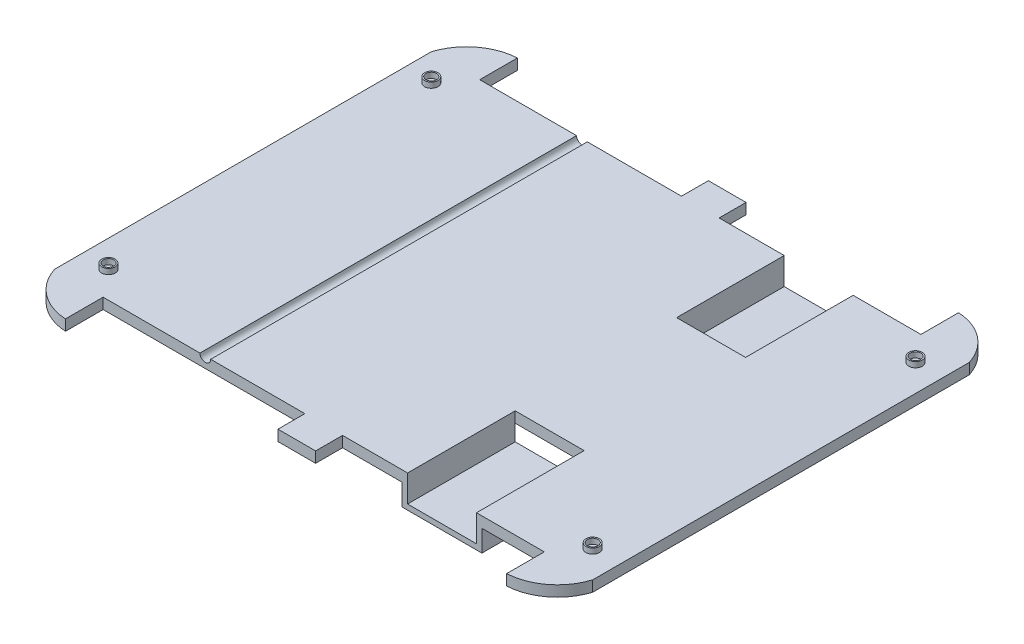
SolidWorks part; units mm, degrees
ref_plane "Front Plane" through (0, 0, 0) normal (0, 0, 1) x (1, 0, 0)
ref_plane "Top Plane" through (0, 0, 0) normal (0, 1, 0) x (1, 0, 0)
ref_plane "Right Plane" through (0, 0, 0) normal (1, 0, 0) x (0, 0, -1)
sketch "Sketch1" plane through (0, 0, 0) normal (0, 1, 0) x (1, 0, 0)
  line L0 (-75.9051, 0) -> (0, 0) construction
  line L1 (-3.5, 35) -> (-3.5, 40)
  line L2 (-50, -35) -> (-50, 35)
  line L3 (-41, 42) -> (0, 42)
  line L4 (3.5, 35) -> (3.5, 40)
  line L5 (41, 35) -> (3.5, 35)
  line L7 (-75.9051, 35) -> (0, 35) construction
  line L8 (-41, 35) -> (-41, 42)
  line L9 (0, -65.306) -> (0, 75.0053) construction
  line L10 (41, 35) -> (41, 42)
  line L12 (-41, 35) -> (-3.5, 35)
  line L13 (-3.5, 40) -> (3.5, 40)
  line L14 (50, 35) -> (41, 42)
  line L15 (50, -35) -> (50, 35)
  line L16 (50, -35) -> (41, -42)
  line L17 (41, -35) -> (41, -42)
  line L18 (41, -35) -> (3.5, -35)
  line L19 (3.5, -35) -> (3.5, -40)
  line L20 (-3.5, -40) -> (3.5, -40)
  line L21 (-3.5, -35) -> (-3.5, -40)
  line L22 (-41, -35) -> (-3.5, -35)
  line L23 (-41, -35) -> (-41, -42)
  line L24 (-50, -35) -> (-41, -42)
  arc A0 (-50, 35) -> (-41, 42) centre (-40.456, 32.0148) cw
  arc A1 (-50, -35) -> (-41, -42) centre (-40.456, -32.0148) ccw
  arc A2 (50, -35) -> (41, -42) centre (40.456, -32.0148) cw
  arc A3 (50, 35) -> (41, 42) centre (40.456, 32.0148) ccw
  point P1 (0, 0)
  point P10 (0, 40)
  point P26 (50, 0)
  point P35 (-50, 0)
  dimension "D7" = 10
  dimension "D1" = 42
  dimension "D2" = 50
  dimension "D3" = 35
  dimension "D4" = 9
  dimension "D5" = 3.5
  dimension "D6" = 40
extrude "Boss-Extrude2" add sketch "Sketch1" along normal blind 2 contours L2 L24 L23 L22 L21 L20 L19 L18 L17 L16 L15 L14 L10 L5 L4 L13 L1 L12 L8 | L24 A1 | A2 L16 | L14 A3 region at (-0.0881, 0, -0.0749) region at (-45.9417, 0, 39.0679) region at (45.9417, 0, -39.0679) region at (45.9417, 0, 39.0679)
sketch "Sketch4" plane through (0, 0, 0) normal (0, 0, 1) x (1, 0, 0)
  line L3 (-41, 0) -> (-3.5, 0) construction
  circle A0 centre (-22, 2) radius 1
  dimension "D1" = 2
  dimension "D6" = 2
  dimension "D4" = 22
extrude "Cut-Extrude4" cut sketch "Sketch4" against normal through all both and the other way through all
ref_plane "Plane1" through (0, 0, 50) normal (0, 0, 1) x (1, 0, 0)
sketch "Sketch6" plane through (0, 0, 50) normal (0, 0, 1) x (1, 0, 0)
  line L0 (41, 0) -> (3.5, 0) construction
  line L1 (21, 2) -> (21, 1)
  line L2 (21, 1) -> (23, 1)
  line L3 (23, 1) -> (23, 2)
  line L4 (15.595, 0) -> (14.595, 0)
  line L5 (15.595, -3) -> (28.405, -3)
  line L6 (15.595, -3) -> (15.595, 8)
  line L7 (15.595, 8) -> (28.405, 8)
  line L8 (28.405, -3) -> (28.405, 8)
  line L9 (14.595, 0) -> (14.595, -4)
  line L10 (14.595, -4) -> (29.405, -4)
  line L11 (29.405, -4) -> (29.405, 0)
  line L12 (29.405, 0) -> (28.405, 0)
  line L13 (15.595, 0) -> (15.595, 2)
  line L14 (15.595, 2) -> (28.405, 2)
  line L15 (41, 2) -> (3.5, 2) construction
  line L16 (28.405, 2) -> (28.405, 0)
  arc A0 (23, 2) -> (21, 2) centre (22, 2) ccw
  dimension "D2" = 2
  dimension "D1" = 22
  dimension "D3" = 2
  dimension "D4" = 4
  dimension "D5" = 6.405
  dimension "D6" = 6.405
  dimension "D7" = 6
  dimension "D8" = 1
  dimension "D9" = 1
  dimension "D10" = 1
extrude "Boss-Extrude3" add sketch "Sketch6" against normal blind 20 from offset 15 contours L11 L12 L8 L5 L6 L4 L9 L10 region at (15.4416, -1.5, 50) offset against normal yes
extrude "Boss-Extrude4" add sketch "Sketch6<3>" along normal blind 20 from offset 85 contours L11 L12 L8 L5 L6 L4 L9 L10 region at (15.4416, -1.5, 50) offset against normal yes
sketch "Sketch6<3>" plane through (0, 0, 50) normal (0, 0, 1) x (1, 0, 0) same geometry as "Sketch6"
extrude "Cut-Extrude5" cut sketch "Sketch6<4>" against normal blind 40 and the other way blind 1 from offset 5 contours L14 L6 L5 L8 L3 L2 L1 | L14 L1 L2 L3 region at (22, 1.5, 50) region at (22, -0.5645, 50)
sketch "Sketch6<4>" plane through (0, 0, 50) normal (0, 0, 1) x (1, 0, 0) same geometry as "Sketch6"
extrude "Cut-Extrude6" cut sketch "Sketch6<6>" against normal blind 20 from offset 65 contours L14 L6 L5 L8 L3 L2 L1 | L14 L1 L2 L3 region at (22, 1.5, 50) region at (22, -0.5645, 50) offset against normal yes
sketch "Sketch6<6>" plane through (0, 0, 50) normal (0, 0, 1) x (1, 0, 0) same geometry as "Sketch6"
ref_plane "Plane3" through (0, 0, 50) normal (0, 0, 1) x (1, 0, 0)
sketch "Sketch11" plane through (0, 2, 0) normal (0, 1, 0) x (1, 0, 0)
  line L0 (0, 0) -> (0, 43.4015) construction
  line L1 (0, 0) -> (-54.0483, 0) construction
  line L3 (-50, -35) -> (-50, 35) construction
  line L4 (-41, 35) -> (-23, 35) construction
  circle A0 centre (-45, 30) radius 1
  circle A1 centre (-45, 30) radius 1.25
  circle A2 centre (45, 30) radius 1
  circle A3 centre (45, 30) radius 1.25
  circle A4 centre (-45, -30) radius 1
  circle A5 centre (-45, -30) radius 1.25
  circle A6 centre (45, -30) radius 1.25
  circle A7 centre (45, -30) radius 1
  dimension "D1" = 2
  dimension "D2" = 5
  dimension "D4" = 2.5
  dimension "D3" = 5
extrude "Boss-Extrude6" add sketch "Sketch11" along normal blind 1
sketch "Sketch12" plane through (0, 2, 0) normal (0, 1, 0) x (1, 0, 0)
  line L22 (28.405, 35) -> (28.405, 15)
  line L23 (28.405, 35) -> (28.405, 15)
  line L24 (28.405, 15) -> (15.595, 15)
  line L25 (50, -35) -> (50, 35)
  line L26 (28.405, 15) -> (15.595, 15)
  line L27 (41, 42) -> (41, 35)
  line L28 (41, 35) -> (28.405, 35)
  line L29 (15.595, 15) -> (15.595, 35)
  line L30 (15.595, 15) -> (15.595, 35)
  line L31 (15.595, 35) -> (3.5, 35)
  line L32 (15.595, 35) -> (3.5, 35)
  line L33 (3.5, 35) -> (3.5, 40)
  line L34 (3.5, 40) -> (-3.5, 40)
  line L35 (-3.5, 40) -> (-3.5, 35)
  line L36 (-3.5, 35) -> (-21, 35)
  line L37 (-21, 35) -> (-21, -35)
  line L38 (-21, -35) -> (-3.5, -35)
  line L39 (-3.5, -35) -> (-3.5, -40)
  line L40 (-3.5, -40) -> (3.5, -40)
  line L41 (3.5, -40) -> (3.5, -35)
  line L42 (3.5, -35) -> (15.595, -35)
  line L43 (15.595, -35) -> (15.595, -15)
  line L44 (15.595, -15) -> (28.405, -15)
  line L45 (28.405, -15) -> (28.405, -35)
  line L46 (28.405, -35) -> (41, -35)
  line L47 (41, -35) -> (41, -42)
  line L49 (50, -35) -> (50, 35)
  line L51 (41, 42) -> (41, 35)
  line L52 (41, 35) -> (28.405, 35)
  line L57 (3.5, 35) -> (3.5, 40)
  line L58 (3.5, 40) -> (-3.5, 40)
  line L59 (-3.5, 40) -> (-3.5, 35)
  line L60 (-3.5, 35) -> (-21, 35)
  line L61 (-21, 35) -> (-21, -35)
  line L62 (-21, -35) -> (-3.5, -35)
  line L63 (-3.5, -35) -> (-3.5, -40)
  line L64 (-3.5, -40) -> (3.5, -40)
  line L65 (3.5, -40) -> (3.5, -35)
  line L66 (3.5, -35) -> (15.595, -35)
  line L67 (15.595, -35) -> (15.595, -15)
  line L68 (15.595, -15) -> (28.405, -15)
  line L69 (28.405, -15) -> (28.405, -35)
  line L70 (28.405, -35) -> (41, -35)
  line L71 (41, -35) -> (41, -42)
  arc A2 (41, -42) -> (50, -35) centre (40.456, -32.0148) ccw
  arc A3 (41, -42) -> (50, -35) centre (40.456, -32.0148) ccw
  arc A4 (50, 35) -> (41, 42) centre (40.456, 32.0148) ccw
  arc A5 (50, 35) -> (41, 42) centre (40.456, 32.0148) ccw
  dimension "D1" = 0
equation "\"ถ\"=4.7"
